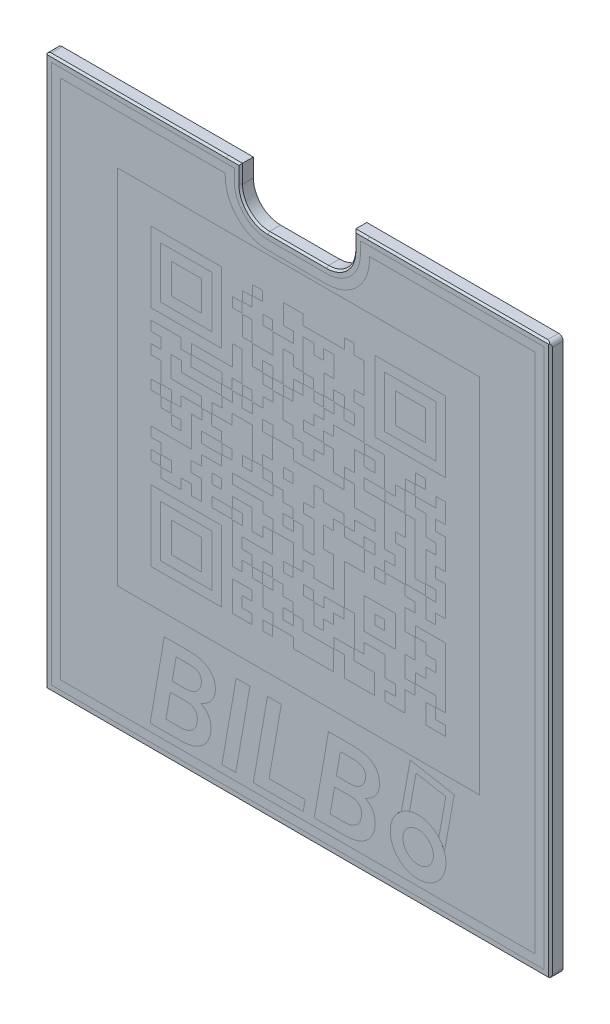
SolidWorks part; units mm, degrees
ref_plane "Front Plane" through (0, 0, 0) normal (0, 0, 1) x (1, 0, 0)
ref_plane "Top Plane" through (0, 0, 0) normal (0, 1, 0) x (1, 0, 0)
ref_plane "Right Plane" through (0, 0, 0) normal (1, 0, 0) x (0, 0, -1)
sketch "Sketch1" plane through (0, 0, 0) normal (0, 0, 1) x (1, 0, 0)
  line L0 (48, -68) -> (-48, -68) construction
  line L1 (56, -32.5) -> (56, -60) construction
  line L2 (56, 46) -> (56, -24.5) construction
  line L3 (-56, -24.5) -> (-56, 46) construction
  line L5 (-15, 54.4) -> (-15, 29) construction
  line L6 (-15, 29) -> (15, 29) construction
  line L7 (15, 29) -> (15, 54) construction
  line L8 (48, 54) -> (15, 54) construction
  line L9 (48, -68) -> (-48, -68) construction
  line L10 (56, -32.5) -> (56, -60) construction
  line L11 (56, 46) -> (56, -24.5) construction
  line L12 (-56, -24.5) -> (-56, 46) construction
  line L13 (-15, 54.4) -> (-48, 54.4) construction
  line L14 (-15, 54.4) -> (-15, 29) construction
  line L15 (-15, 29) -> (15, 29) construction
  line L16 (15, 29) -> (15, 54) construction
  line L17 (48, 54) -> (15, 54) construction
  line L18 (-15.25, 54.05) -> (-15.25, 28.75)
  line L19 (-55.65, 54.05) -> (-15.25, 54.05)
  line L20 (-55.65, 54.05) -> (-55.65, -67.65)
  line L21 (-55.65, -67.65) -> (55.825, -67.65)
  line L22 (55.825, 54.05) -> (55.825, -67.65)
  line L23 (-15.25, 28.75) -> (15.125, 28.75)
  line L24 (15.125, 28.75) -> (15.125, 54.05)
  line L25 (15.125, 54.05) -> (55.825, 54.05)
  arc A1 (-49.5246, -64.05) -> (-52.475, -61.2455) centre (-52, -63.7) ccw construction
  arc A2 (-53.35, 50.3) -> (-52, 48.95) centre (-52, 50.3) ccw construction
  circle A5 centre (-52, -63.7) radius 2.1 construction
  circle A6 centre (-52, 2.9) radius 2.15 construction
  circle A7 centre (52, 2.9) radius 2.15 construction
  circle A8 centre (52, 50.3) radius 2.1 construction
  circle A9 centre (-52, 50.3) radius 2.1 construction
  circle A10 centre (-52, 50.3) radius 1.35
  circle A11 centre (-52, 2.9) radius 1.35
  circle A12 centre (-52, -63.7) radius 1.35
  circle A13 centre (52, 50.3) radius 1.35
  circle A14 centre (52, 2.9) radius 1.35
  circle A15 centre (52, -63.7) radius 1.35
  circle A16 centre (-52, 2.9) radius 2.15 construction
  circle A17 centre (52, 2.9) radius 2.15 construction
  arc A18 (52, 48.95) -> (53.35, 50.3) centre (52, 50.3) ccw construction
  arc A19 (53.35, -65.8042) -> (53.35, -61.5958) centre (52, -63.7) ccw construction
  dimension "D5" = 2.7
  dimension "D1" = 0.35
  dimension "D2" = 0.35
  dimension "D3" = 0.35
  dimension "D4" = 0.35
  dimension "D6" = 0.25
  dimension "D7" = 0.25
  dimension "D8" = 0.25
extrude "Boss-Extrude1" add sketch "Sketch1" along normal blind 2.8
sketch "Sketch2" plane through (0, 0, 2.8) normal (0, 0, 1) x (1, 0, 0)
  line L5 (15.125, 28.75) -> (-15.25, 28.75) construction
  line L8 (-45.5, -63.25) -> (45.5, -63.25)
  line L9 (-45.5, -63.25) -> (-45.5, 27.75)
  line L10 (-45.5, 27.75) -> (45.5, 27.75)
  line L11 (45.5, -63.25) -> (45.5, 27.75)
  line L31 (-42, 24.25) -> (-28, 24.25)
  line L32 (-42, 24.25) -> (-42, 10.25)
  line L33 (-42, 10.25) -> (-28, 10.25)
  line L34 (-28, 24.25) -> (-28, 10.25)
  line L35 (-28, 24.25) -> (-14, 24.25)
  line L36 (-28, 24.25) -> (-28, 10.25)
  line L37 (-28, 10.25) -> (-14, 10.25)
  line L38 (-14, 24.25) -> (-14, 10.25)
  line L39 (-14, 24.25) -> (0, 24.25)
  line L40 (-14, 24.25) -> (-14, 10.25)
  line L41 (-14, 10.25) -> (0, 10.25)
  line L42 (0, 24.25) -> (0, 10.25)
  line L43 (0, 24.25) -> (14, 24.25)
  line L44 (0, 24.25) -> (0, 10.25)
  line L45 (0, 10.25) -> (14, 10.25)
  line L46 (14, 24.25) -> (14, 10.25)
  line L47 (14, 24.25) -> (28, 24.25)
  line L48 (14, 24.25) -> (14, 10.25)
  line L49 (14, 10.25) -> (28, 10.25)
  line L50 (28, 24.25) -> (28, 10.25)
  line L51 (28, 24.25) -> (42, 24.25)
  line L52 (28, 24.25) -> (28, 10.25)
  line L53 (28, 10.25) -> (42, 10.25)
  line L54 (42, 24.25) -> (42, 10.25)
  line L55 (-42, 10.25) -> (-28, 10.25)
  line L56 (-42, 10.25) -> (-42, -3.75)
  line L57 (-42, -3.75) -> (-28, -3.75)
  line L58 (-28, 10.25) -> (-28, -3.75)
  line L59 (-28, -3.75) -> (-14, -3.75)
  line L60 (-28, -3.75) -> (-28, 10.25)
  line L61 (-28, 10.25) -> (-14, 10.25)
  line L62 (-14, -3.75) -> (-14, 10.25)
  line L63 (-14, -3.75) -> (0, -3.75)
  line L64 (-14, -3.75) -> (-14, 10.25)
  line L65 (-14, 10.25) -> (0, 10.25)
  line L66 (0, -3.75) -> (0, 10.25)
  line L67 (0, -3.75) -> (14, -3.75)
  line L68 (0, -3.75) -> (0, 10.25)
  line L69 (0, 10.25) -> (14, 10.25)
  line L70 (14, -3.75) -> (14, 10.25)
  line L71 (14, -3.75) -> (28, -3.75)
  line L72 (14, -3.75) -> (14, 10.25)
  line L73 (14, 10.25) -> (28, 10.25)
  line L74 (28, -3.75) -> (28, 10.25)
  line L75 (28, -3.75) -> (42, -3.75)
  line L76 (28, -3.75) -> (28, 10.25)
  line L77 (28, 10.25) -> (42, 10.25)
  line L78 (42, -3.75) -> (42, 10.25)
  line L79 (42, -3.75) -> (28, -3.75)
  line L80 (42, -3.75) -> (42, -17.75)
  line L81 (42, -17.75) -> (28, -17.75)
  line L82 (28, -3.75) -> (28, -17.75)
  line L83 (14, -3.75) -> (28, -3.75)
  line L84 (14, -3.75) -> (14, -17.75)
  line L85 (14, -17.75) -> (28, -17.75)
  line L86 (28, -3.75) -> (28, -17.75)
  line L87 (0, -3.75) -> (14, -3.75)
  line L88 (0, -3.75) -> (0, -17.75)
  line L89 (0, -17.75) -> (14, -17.75)
  line L90 (14, -3.75) -> (14, -17.75)
  line L91 (-14, -3.75) -> (0, -3.75)
  line L92 (-14, -3.75) -> (-14, -17.75)
  line L93 (-14, -17.75) -> (0, -17.75)
  line L94 (0, -3.75) -> (0, -17.75)
  line L95 (-28, -3.75) -> (-14, -3.75)
  line L96 (-28, -3.75) -> (-28, -17.75)
  line L97 (-28, -17.75) -> (-14, -17.75)
  line L98 (-14, -3.75) -> (-14, -17.75)
  line L99 (-42, -3.75) -> (-28, -3.75)
  line L100 (-42, -3.75) -> (-42, -17.75)
  line L101 (-42, -17.75) -> (-28, -17.75)
  line L102 (-28, -3.75) -> (-28, -17.75)
  line L103 (-42, -17.75) -> (-28, -17.75)
  line L104 (-42, -17.75) -> (-42, -31.75)
  line L105 (-42, -31.75) -> (-28, -31.75)
  line L106 (-28, -17.75) -> (-28, -31.75)
  line L107 (-28, -31.75) -> (-14, -31.75)
  line L108 (-28, -31.75) -> (-28, -17.75)
  line L109 (-28, -17.75) -> (-14, -17.75)
  line L110 (-14, -31.75) -> (-14, -17.75)
  line L111 (-14, -17.75) -> (0, -17.75)
  line L112 (-14, -17.75) -> (-14, -31.75)
  line L113 (-14, -31.75) -> (0, -31.75)
  line L114 (0, -17.75) -> (0, -31.75)
  line L115 (0, -31.75) -> (14, -31.75)
  line L116 (0, -31.75) -> (0, -17.75)
  line L117 (0, -17.75) -> (14, -17.75)
  line L118 (14, -31.75) -> (14, -17.75)
  line L119 (14, -31.75) -> (28, -31.75)
  line L120 (14, -31.75) -> (14, -17.75)
  line L121 (14, -17.75) -> (28, -17.75)
  line L122 (28, -31.75) -> (28, -17.75)
  line L123 (28, -31.75) -> (42, -31.75)
  line L124 (28, -31.75) -> (28, -17.75)
  line L125 (28, -17.75) -> (42, -17.75)
  line L126 (42, -31.75) -> (42, -17.75)
  line L127 (-42, -31.75) -> (-28, -31.75)
  line L128 (-42, -31.75) -> (-42, -45.75)
  line L129 (-42, -45.75) -> (-28, -45.75)
  line L130 (-28, -31.75) -> (-28, -45.75)
  line L131 (-28, -45.75) -> (-14, -45.75)
  line L132 (-28, -45.75) -> (-28, -31.75)
  line L133 (-28, -31.75) -> (-14, -31.75)
  line L134 (-14, -45.75) -> (-14, -31.75)
  line L135 (-14, -45.75) -> (0, -45.75)
  line L136 (-14, -45.75) -> (-14, -31.75)
  line L137 (-14, -31.75) -> (0, -31.75)
  line L138 (0, -45.75) -> (0, -31.75)
  line L139 (0, -45.75) -> (14, -45.75)
  line L140 (0, -45.75) -> (0, -31.75)
  line L141 (0, -31.75) -> (14, -31.75)
  line L142 (14, -45.75) -> (14, -31.75)
  line L143 (14, -45.75) -> (28, -45.75)
  line L144 (14, -45.75) -> (14, -31.75)
  line L145 (14, -31.75) -> (28, -31.75)
  line L146 (28, -45.75) -> (28, -31.75)
  line L147 (28, -45.75) -> (42, -45.75)
  line L148 (28, -45.75) -> (28, -31.75)
  line L149 (28, -31.75) -> (42, -31.75)
  line L150 (42, -45.75) -> (42, -31.75)
  line L151 (42, -45.75) -> (28, -45.75)
  line L152 (42, -45.75) -> (42, -59.75)
  line L153 (42, -59.75) -> (28, -59.75)
  line L154 (28, -45.75) -> (28, -59.75)
  line L155 (28, -59.75) -> (14, -59.75)
  line L156 (28, -59.75) -> (28, -45.75)
  line L157 (28, -45.75) -> (14, -45.75)
  line L158 (14, -59.75) -> (14, -45.75)
  line L159 (0, -45.75) -> (14, -45.75)
  line L160 (0, -45.75) -> (0, -59.75)
  line L161 (0, -59.75) -> (14, -59.75)
  line L162 (14, -45.75) -> (14, -59.75)
  line L163 (-14, -45.75) -> (0, -45.75)
  line L164 (-14, -45.75) -> (-14, -59.75)
  line L165 (-14, -59.75) -> (0, -59.75)
  line L166 (0, -45.75) -> (0, -59.75)
  line L167 (-28, -45.75) -> (-14, -45.75)
  line L168 (-28, -45.75) -> (-28, -59.75)
  line L169 (-28, -59.75) -> (-14, -59.75)
  line L170 (-14, -45.75) -> (-14, -59.75)
  line L171 (-42, -45.75) -> (-28, -45.75)
  line L172 (-42, -45.75) -> (-42, -59.75)
  line L173 (-42, -59.75) -> (-28, -59.75)
  line L174 (-28, -45.75) -> (-28, -59.75)
  point P3 (0, 27.75)
  point P58 (-45.5, -17.75)
  dimension "D1" = 1
  dimension "D2" = 91
  dimension "D3" = 14
sketch "Sketch3" plane through (0, 0, 2.8) normal (0, 0, 1) x (1, 0, 0)
  circle A0 centre (-52, 50.3) radius 2.5
  circle A1 centre (-52, 2.9) radius 2.5
  circle A2 centre (-52, -63.7) radius 2.5
  circle A3 centre (52, -63.7) radius 2.5
  circle A4 centre (52, 2.9) radius 2.5
  circle A5 centre (52, 50.3) radius 2.5
  dimension "D1" = 5
extrude "Cut-Extrude1" cut sketch "Sketch3" against normal blind 2.2
sketch "Sketch4" plane through (0, 0, 0) normal (0, 0, -1) x (-1, 0, 0)
  line L0 (-15.125, 28.75) -> (15.25, 28.75) construction
  line L1 (-45.65, -57.65) -> (45.65, -57.65)
  line L2 (-45.65, -57.65) -> (-45.65, 27.75)
  line L3 (-45.65, 27.75) -> (45.65, 27.75)
  line L4 (45.65, -57.65) -> (45.65, 27.75)
  line L5 (-45.65, -57.65) -> (45.65, 27.75) construction
  line L6 (-45.65, 27.75) -> (45.65, -57.65) construction
  line L7 (55.65, 54.05) -> (55.65, -67.65) construction
  line L8 (55.65, -67.65) -> (-55.825, -67.65) construction
  point P0 (0, -14.95)
  point P9 (0, 27.75)
  dimension "D1" = 1
  dimension "D2" = 10
  dimension "D3" = 10
extrude "Cut-Extrude2" cut sketch "Sketch4" against normal blind 1.5
sketch "Sketch5" plane through (0, 0, 0.6) normal (0, 0, 1) x (1, 0, 0)
  line L2 (-53.35, 48.1958) -> (-53.35, 52.4042)
  line L4 (-50.65, 48.1958) -> (-50.65, 52.4042)
  line L5 (-53.35, 48.1958) -> (-50.65, 52.4042) construction
  line L6 (-53.35, 52.4042) -> (-50.65, 48.1958) construction
  line L8 (-53.35, 0.7958) -> (-53.35, 5.0042)
  line L10 (-50.65, 0.7958) -> (-50.65, 5.0042)
  line L11 (-53.35, 0.7958) -> (-50.65, 5.0042) construction
  line L12 (-53.35, 5.0042) -> (-50.65, 0.7958) construction
  line L14 (-53.35, -65.8042) -> (-53.35, -61.5958)
  line L16 (-50.65, -65.8042) -> (-50.65, -61.5958)
  line L17 (-53.35, -65.8042) -> (-50.65, -61.5958) construction
  line L18 (-53.35, -61.5958) -> (-50.65, -65.8042) construction
  circle A0 centre (-52, 50.3) radius 2.5 construction
  circle A1 centre (-52, 50.3) radius 1.35 construction
  arc A2 (-50.65, 52.4042) -> (-53.35, 52.4042) centre (-52, 50.3) ccw
  arc A3 (-53.35, 48.1958) -> (-50.65, 48.1958) centre (-52, 50.3) ccw
  circle A4 centre (-52, 2.9) radius 2.5 construction
  circle A5 centre (-52, 2.9) radius 1.35 construction
  circle A6 centre (-52, 2.9) radius 2.5 construction
  arc A7 (-50.65, 5.0042) -> (-53.35, 5.0042) centre (-52, 2.9) ccw
  arc A8 (-53.35, 0.7958) -> (-50.65, 0.7958) centre (-52, 2.9) ccw
  circle A9 centre (-52, -63.7) radius 2.5 construction
  circle A10 centre (-52, -63.7) radius 1.35 construction
  circle A11 centre (-52, -63.7) radius 2.5 construction
  arc A12 (-50.65, -61.5958) -> (-53.35, -61.5958) centre (-52, -63.7) ccw
  arc A13 (-53.35, -65.8042) -> (-50.65, -65.8042) centre (-52, -63.7) ccw
  point P0 (-52, 50.3)
  point P10 (-52, 2.9)
  point P22 (-52, -63.7)
extrude "Cut-Extrude3" cut sketch "Sketch5" against normal blind 0.2
sketch "Sketch6" plane through (0, 0, 0.4) normal (0, 0, 1) x (1, 0, 0)
  line L0 (-50.65, -65.8042) -> (-50.65, -61.5958) construction
  line L1 (-53.35, -65.05) -> (-50.65, -65.05)
  line L2 (-53.35, -65.05) -> (-53.35, -62.35)
  line L3 (-53.35, -62.35) -> (-50.65, -62.35)
  line L4 (-50.65, -65.05) -> (-50.65, -62.35)
  line L5 (-53.35, -65.05) -> (-50.65, -62.35) construction
  line L6 (-53.35, -62.35) -> (-50.65, -65.05) construction
  line L7 (-50.65, 0.7958) -> (-50.65, 5.0042) construction
  line L8 (-53.35, 1.55) -> (-50.65, 1.55)
  line L9 (-53.35, 1.55) -> (-53.35, 4.25)
  line L10 (-53.35, 4.25) -> (-50.65, 4.25)
  line L11 (-50.65, 1.55) -> (-50.65, 4.25)
  line L12 (-53.35, 1.55) -> (-50.65, 4.25) construction
  line L13 (-53.35, 4.25) -> (-50.65, 1.55) construction
  line L14 (-50.65, 48.1958) -> (-50.65, 52.4042) construction
  line L15 (-53.35, 48.95) -> (-50.65, 48.95)
  line L16 (-53.35, 48.95) -> (-53.35, 51.65)
  line L17 (-53.35, 51.65) -> (-50.65, 51.65)
  line L18 (-50.65, 48.95) -> (-50.65, 51.65)
  line L19 (-53.35, 48.95) -> (-50.65, 51.65) construction
  line L20 (-53.35, 51.65) -> (-50.65, 48.95) construction
  arc A0 (-50.65, -63.7) -> (-53.35, -63.7) centre (-52, -63.7) ccw construction
  arc A1 (-50.65, 2.9) -> (-53.35, 2.9) centre (-52, 2.9) ccw construction
  arc A2 (-50.65, 50.3) -> (-53.35, 50.3) centre (-52, 50.3) ccw construction
  point P0 (-52, -63.7)
  point P11 (-52, 2.9)
  point P22 (-52, 50.3)
extrude "Cut-Extrude4" cut sketch "Sketch6" against normal blind 0.2
mirror "Mirror1" about plane through (0, 0, 0) normal (1, 0, 0) of "Cut-Extrude4", "Cut-Extrude3"
chamfer "Chamfer1" distance 0.4 angle 45 8 edges at (0.0875, -67.65, 2.8) (55.825, -6.8, 2.8) (35.475, 54.05, 2.8) (15.125, 41.4, 2.8) (-0.0625, 28.75, 2.8) (-15.25, 41.4, 2.8) (-35.45, 54.05, 2.8) (-55.65, -6.8, 2.8)
sketch "Sketch11" plane through (0, 0, 2.8) normal (0, 0, 1) x (1, 0, 0)
  line L0 (15.125, 54.05) -> (55.825, 54.05) construction
  line L1 (-15.65, 28.35) -> (15.525, 28.35)
  line L2 (-15.65, 28.35) -> (-15.65, 54.05)
  line L3 (-15.65, 54.05) -> (15.525, 54.05)
  line L4 (15.525, 28.35) -> (15.525, 54.05)
  line L5 (15.525, 53.65) -> (15.525, 28.35) construction
extrude "Boss-Extrude4" add sketch "Sketch11" against normal up to surface (2.8 mm away) up to face at (0, -14.95, 0)
chamfer "Chamfer2" distance 0.4 angle 45 1 edges at (-0.0625, 54.05, 2.8)
sketch "Sketch12" plane through (0, 0, 2.8) normal (0, 0, 1) x (1, 0, 0)
  circle A0 centre (52, -63.7) radius 2.5 construction
  circle A1 centre (52, 50.3) radius 2.5 construction
  circle A2 centre (52, 2.9) radius 2.5 construction
  circle A3 centre (-52, -63.7) radius 2.5 construction
  circle A4 centre (-52, 2.9) radius 2.5 construction
  circle A5 centre (-52, 50.3) radius 2.5 construction
  circle A6 centre (52, -63.7) radius 2.5
  circle A7 centre (52, 50.3) radius 2.5
  circle A8 centre (52, 2.9) radius 2.5
  circle A9 centre (-52, -63.7) radius 2.5
  circle A10 centre (-52, 2.9) radius 2.5
  circle A11 centre (-52, 50.3) radius 2.5
extrude "Boss-Extrude5" add sketch "Sketch12" against normal up to surface (2.8 mm away) up to face at (0.0875, -6.8, 0)
sketch "Sketch13" plane through (0, 0, 0) normal (0, 0, -1) x (-1, 0, 0)
  line L0 (-55.825, -67.65) -> (-55.825, 54.05) construction
  line L1 (-50.825, 49.05) -> (50.825, 49.05) construction
  line L2 (-50.825, 49.05) -> (-50.825, -62.65) construction
  line L3 (-50.825, -62.65) -> (50.825, -62.65) construction
  line L4 (50.825, 49.05) -> (50.825, -62.65) construction
  line L5 (-55.825, 54.05) -> (55.65, 54.05) construction
  line L6 (55.65, -67.65) -> (-55.825, -67.65) construction
  circle A0 centre (-50.825, 49.05) radius 3.2
  circle A1 centre (50.825, 49.05) radius 3.2
  circle A2 centre (50.825, -62.65) radius 3.2
  circle A3 centre (-50.825, -62.65) radius 3.2
  circle A4 centre (-50.825, -6.8) radius 3.2
  circle A5 centre (50.825, -6.8) radius 3.2
  point P4 (0, 49.05)
  dimension "D1" = 6.4
  dimension "D2" = 5
  dimension "D3" = 5
  dimension "D4" = 5
extrude "Cut-Extrude7" cut sketch "Sketch13" against normal blind 1.2
sketch "Sketch14" plane through (0, 0, 2.8) normal (0, 0, 1) x (1, 0, 0)
  line L0 (-55.65, 54.05) -> (-15.65, 54.05) construction
  line L1 (-12.5, 54.05) -> (12.5, 54.05)
  line L2 (-12.5, 54.05) -> (-12.5, 44.05)
  line L3 (-12.5, 44.05) -> (12.5, 44.05)
  line L4 (12.5, 54.05) -> (12.5, 44.05)
  point P6 (0, 44.05)
  dimension "D1" = 25
  dimension "D2" = 10
extrude "Cut-Extrude8" cut sketch "Sketch14" against normal through all
fillet "Fillet1" radius 6 2 edges at (12.5, 44.05, 1.4) (-12.5, 44.05, 1.4)
chamfer "Chamfer3" distance 0.4 angle 45 5 edges at (-12.5, 51.85, 2.8) (12.5, 51.85, 2.8) (-10.7426, 45.8074, 2.8) (10.7426, 45.8074, 2.8) (0, 44.05, 2.8)
sketch "Sketch22" plane through (0, 0, 2.8) normal (0, 0, 1) x (1, 0, 0)
  line L0 (-39.7032, 39.7992) -> (40.1257, 39.7992)
  line L1 (40.1257, 39.7992) -> (40.1257, -40.0298)
  line L2 (40.1257, -40.0298) -> (-39.7032, -40.0298)
  line L3 (-39.7032, -40.0298) -> (-39.7032, 39.7992)
  line L4 (-32.2887, 30.1954) -> (-32.2887, 16.7799)
  line L5 (-32.2887, 16.7799) -> (-16.6839, 16.7799)
  line L6 (-16.6839, 16.7799) -> (-16.6839, 32.3847)
  line L7 (-16.6839, 32.3847) -> (-32.2887, 32.3847)
  line L8 (-32.2887, 32.3847) -> (-32.2887, 30.1954)
  line L9 (-9.8364, 30.2513) -> (-7.703, 30.2513)
  line L10 (-7.703, 30.2513) -> (-7.703, 32.3847)
  line L11 (-7.703, 32.3847) -> (-9.8364, 32.3847)
  line L12 (-9.8364, 32.3847) -> (-9.8364, 30.2513)
  line L13 (-3.1007, 30.1954) -> (-3.1007, 28.006)
  line L14 (-3.1007, 28.006) -> (-0.8554, 28.006)
  line L15 (-0.8554, 28.006) -> (-0.8554, 25.649)
  line L16 (-0.8554, 25.649) -> (-5.3459, 25.649)
  line L17 (-5.3459, 25.649) -> (-5.3459, 21.1585)
  line L18 (-5.3459, 21.1585) -> (-9.8364, 21.1585)
  line L19 (-9.8364, 21.1585) -> (-9.8364, 16.7799)
  line L20 (-9.8364, 16.7799) -> (-7.703, 16.7799)
  line L21 (-7.703, 16.7799) -> (-7.703, 19.0251)
  line L22 (-7.703, 19.0251) -> (-5.3459, 19.0251)
  line L23 (-5.3459, 19.0251) -> (-5.3459, 16.7799)
  line L24 (-5.3459, 16.7799) -> (-3.2125, 16.7799)
  line L25 (-3.2125, 16.7799) -> (-3.2125, 23.5156)
  line L26 (-3.2125, 23.5156) -> (-0.8554, 23.5156)
  line L27 (-0.8554, 23.5156) -> (-0.8554, 21.2703)
  line L28 (-0.8554, 21.2703) -> (1.278, 21.2703)
  line L29 (1.278, 21.2703) -> (1.278, 28.006)
  line L30 (1.278, 28.006) -> (3.635, 28.006)
  line L31 (3.635, 28.006) -> (3.635, 25.7608)
  line L32 (3.635, 25.7608) -> (5.7684, 25.7608)
  line L33 (5.7684, 25.7608) -> (5.7684, 28.006)
  line L34 (5.7684, 28.006) -> (8.1255, 28.006)
  line L35 (8.1255, 28.006) -> (8.1255, 23.4037)
  line L36 (8.1255, 23.4037) -> (5.8803, 23.4037)
  line L37 (5.8803, 23.4037) -> (5.8803, 19.0251)
  line L38 (5.8803, 19.0251) -> (8.0137, 19.0251)
  line L39 (8.0137, 19.0251) -> (8.0137, 21.2703)
  line L40 (8.0137, 21.2703) -> (10.3707, 21.2703)
  line L41 (10.3707, 21.2703) -> (10.3707, 19.0251)
  line L42 (10.3707, 19.0251) -> (12.616, 19.0251)
  line L43 (12.616, 19.0251) -> (12.616, 16.668)
  line L44 (12.616, 16.668) -> (10.2589, 16.668)
  line L45 (10.2589, 16.668) -> (10.2589, 18.9133)
  line L46 (10.2589, 18.9133) -> (8.1255, 18.9133)
  line L47 (8.1255, 18.9133) -> (8.1255, 16.668)
  line L48 (8.1255, 16.668) -> (5.8803, 16.668)
  line L49 (5.8803, 16.668) -> (5.8803, 14.4228)
  line L50 (5.8803, 14.4228) -> (3.635, 14.4228)
  line L51 (3.635, 14.4228) -> (3.635, 12.1776)
  line L52 (3.635, 12.1776) -> (1.3898, 12.1776)
  line L53 (1.3898, 12.1776) -> (1.3898, 10.0442)
  line L54 (1.3898, 10.0442) -> (5.7684, 10.0442)
  line L55 (5.7684, 10.0442) -> (5.7684, 12.2894)
  line L56 (5.7684, 12.2894) -> (8.0137, 12.2894)
  line L57 (8.0137, 12.2894) -> (8.0137, 14.5346)
  line L58 (8.0137, 14.5346) -> (14.7494, 14.5346)
  line L59 (14.7494, 14.5346) -> (14.7494, 21.1585)
  line L60 (14.7494, 21.1585) -> (12.5041, 21.1585)
  line L61 (12.5041, 21.1585) -> (12.5041, 23.5156)
  line L62 (12.5041, 23.5156) -> (14.7494, 23.5156)
  line L63 (14.7494, 23.5156) -> (14.7494, 30.1394)
  line L64 (14.7494, 30.1394) -> (12.5041, 30.1394)
  line L65 (12.5041, 30.1394) -> (12.5041, 32.3847)
  line L66 (12.5041, 32.3847) -> (10.3707, 32.3847)
  line L67 (10.3707, 32.3847) -> (10.3707, 30.1394)
  line L68 (10.3707, 30.1394) -> (1.278, 30.1394)
  line L69 (1.278, 30.1394) -> (1.278, 32.3847)
  line L70 (1.278, 32.3847) -> (-3.1007, 32.3847)
  line L71 (-3.1007, 32.3847) -> (-3.1007, 30.1954)
  line L72 (17.1064, 30.1954) -> (17.1064, 16.7799)
  line L73 (17.1064, 16.7799) -> (32.7113, 16.7799)
  line L74 (32.7113, 16.7799) -> (32.7113, 32.3847)
  line L75 (32.7113, 32.3847) -> (17.1064, 32.3847)
  line L76 (17.1064, 32.3847) -> (17.1064, 30.1954)
  line L77 (-30.0994, 30.2513) -> (-18.8173, 30.2513)
  line L78 (-18.8173, 30.2513) -> (-18.8173, 18.9133)
  line L79 (-18.8173, 18.9133) -> (-30.1553, 18.9133)
  line L80 (-30.1553, 18.9133) -> (-30.1553, 30.2513)
  line L81 (-30.1553, 30.2513) -> (-30.1273, 30.2513)
  line L82 (-30.1273, 30.2513) -> (-30.0994, 30.2513)
  line L83 (19.2958, 30.2513) -> (30.5778, 30.2513)
  line L84 (30.5778, 30.2513) -> (30.5778, 18.9133)
  line L85 (30.5778, 18.9133) -> (19.2398, 18.9133)
  line L86 (19.2398, 18.9133) -> (19.2398, 30.2513)
  line L87 (19.2398, 30.2513) -> (19.2679, 30.2513)
  line L88 (19.2679, 30.2513) -> (19.2958, 30.2513)
  line L89 (-12.0816, 28.006) -> (-9.9482, 28.006)
  line L90 (-9.9482, 28.006) -> (-9.9482, 30.1394)
  line L91 (-9.9482, 30.1394) -> (-12.0816, 30.1394)
  line L92 (-12.0816, 30.1394) -> (-12.0816, 28.006)
  line L93 (-27.7983, 25.7049) -> (-27.7983, 21.2703)
  line L94 (-27.7983, 21.2703) -> (-21.1744, 21.2703)
  line L95 (-21.1744, 21.2703) -> (-21.1744, 27.8942)
  line L96 (-21.1744, 27.8942) -> (-27.7983, 27.8942)
  line L97 (-27.7983, 27.8942) -> (-27.7983, 25.7049)
  line L98 (-14.3269, 25.7608) -> (-12.1934, 25.7608)
  line L99 (-12.1934, 25.7608) -> (-12.1934, 27.8942)
  line L100 (-12.1934, 27.8942) -> (-14.3269, 27.8942)
  line L101 (-14.3269, 27.8942) -> (-14.3269, 25.7608)
  line L102 (-7.5912, 25.7608) -> (-5.4577, 25.7608)
  line L103 (-5.4577, 25.7608) -> (-5.4577, 27.8942)
  line L104 (-5.4577, 27.8942) -> (-7.5912, 27.8942)
  line L105 (-7.5912, 27.8942) -> (-7.5912, 25.7608)
  line L106 (21.5969, 25.7049) -> (21.5969, 21.2703)
  line L107 (21.5969, 21.2703) -> (28.2208, 21.2703)
  line L108 (28.2208, 21.2703) -> (28.2208, 27.8942)
  line L109 (28.2208, 27.8942) -> (21.5969, 27.8942)
  line L110 (21.5969, 27.8942) -> (21.5969, 25.7049)
  line L111 (-12.0816, 23.4597) -> (-12.0816, 21.2703)
  line L112 (-12.0816, 21.2703) -> (-9.9482, 21.2703)
  line L113 (-9.9482, 21.2703) -> (-9.9482, 25.649)
  line L114 (-9.9482, 25.649) -> (-12.0816, 25.649)
  line L115 (-12.0816, 25.649) -> (-12.0816, 23.4597)
  line L116 (1.3898, 19.0251) -> (3.5232, 19.0251)
  line L117 (3.5232, 19.0251) -> (3.5232, 21.1585)
  line L118 (3.5232, 21.1585) -> (1.3898, 21.1585)
  line L119 (1.3898, 21.1585) -> (1.3898, 19.0251)
  line L120 (-14.3269, 16.7239) -> (-14.3269, 14.4228)
  line L121 (-14.3269, 14.4228) -> (-23.3078, 14.4228)
  line L122 (-23.3078, 14.4228) -> (-23.3078, 12.2894)
  line L123 (-23.3078, 12.2894) -> (-16.5721, 12.2894)
  line L124 (-16.5721, 12.2894) -> (-16.5721, 10.0442)
  line L125 (-16.5721, 10.0442) -> (-14.4387, 10.0442)
  line L126 (-14.4387, 10.0442) -> (-14.4387, 12.2894)
  line L127 (-14.4387, 12.2894) -> (-12.1934, 12.2894)
  line L128 (-12.1934, 12.2894) -> (-12.1934, 18.9133)
  line L129 (-12.1934, 18.9133) -> (-14.3269, 18.9133)
  line L130 (-14.3269, 18.9133) -> (-14.3269, 16.7239)
  line L131 (-0.8554, 16.7799) -> (1.278, 16.7799)
  line L132 (1.278, 16.7799) -> (1.278, 18.9133)
  line L133 (1.278, 18.9133) -> (-0.8554, 18.9133)
  line L134 (-0.8554, 18.9133) -> (-0.8554, 16.7799)
  line L135 (3.635, 16.7799) -> (5.7684, 16.7799)
  line L136 (5.7684, 16.7799) -> (5.7684, 18.9133)
  line L137 (5.7684, 18.9133) -> (3.635, 18.9133)
  line L138 (3.635, 18.9133) -> (3.635, 16.7799)
  line L139 (-7.5912, 14.5346) -> (-5.4577, 14.5346)
  line L140 (-5.4577, 14.5346) -> (-5.4577, 16.668)
  line L141 (-5.4577, 16.668) -> (-7.5912, 16.668)
  line L142 (-7.5912, 16.668) -> (-7.5912, 14.5346)
  line L143 (-3.1007, 14.5346) -> (-0.9673, 14.5346)
  line L144 (-0.9673, 14.5346) -> (-0.9673, 16.668)
  line L145 (-0.9673, 16.668) -> (-3.1007, 16.668)
  line L146 (-3.1007, 16.668) -> (-3.1007, 14.5346)
  line L147 (-32.2887, 12.2894) -> (-30.0435, 12.2894)
  line L148 (-30.0435, 12.2894) -> (-30.0435, 9.9323)
  line L149 (-30.0435, 9.9323) -> (-32.2887, 9.9323)
  line L150 (-32.2887, 9.9323) -> (-32.2887, 7.7989)
  line L151 (-32.2887, 7.7989) -> (-30.0435, 7.7989)
  line L152 (-30.0435, 7.7989) -> (-30.0435, 3.3085)
  line L153 (-30.0435, 3.3085) -> (-27.7983, 3.3085)
  line L154 (-27.7983, 3.3085) -> (-27.7983, 1.0632)
  line L155 (-27.7983, 1.0632) -> (-25.6649, 1.0632)
  line L156 (-25.6649, 1.0632) -> (-25.6649, 3.3085)
  line L157 (-25.6649, 3.3085) -> (-21.1744, 3.3085)
  line L158 (-21.1744, 3.3085) -> (-21.1744, 5.4419)
  line L159 (-21.1744, 5.4419) -> (-27.9101, 5.4419)
  line L160 (-27.9101, 5.4419) -> (-27.9101, 10.0442)
  line L161 (-27.9101, 10.0442) -> (-25.553, 10.0442)
  line L162 (-25.553, 10.0442) -> (-25.553, 7.7989)
  line L163 (-25.553, 7.7989) -> (-16.6839, 7.7989)
  line L164 (-16.6839, 7.7989) -> (-16.6839, 9.9323)
  line L165 (-16.6839, 9.9323) -> (-23.4196, 9.9323)
  line L166 (-23.4196, 9.9323) -> (-23.4196, 12.1776)
  line L167 (-23.4196, 12.1776) -> (-25.6649, 12.1776)
  line L168 (-25.6649, 12.1776) -> (-25.6649, 14.4228)
  line L169 (-25.6649, 14.4228) -> (-32.2887, 14.4228)
  line L170 (-32.2887, 14.4228) -> (-32.2887, 12.2894)
  line L171 (-5.8228, 12.1776) -> (-7.5912, 12.1776)
  line L172 (-7.5912, 12.1776) -> (-7.5912, 9.9323)
  line L173 (-7.5912, 9.9323) -> (-9.8364, 9.9323)
  line L174 (-9.8364, 9.9323) -> (-9.8364, 7.6871)
  line L175 (-9.8364, 7.6871) -> (-12.1934, 7.6871)
  line L176 (-12.1934, 7.6871) -> (-12.1934, 9.9323)
  line L177 (-12.1934, 9.9323) -> (-14.3269, 9.9323)
  line L178 (-14.3269, 9.9323) -> (-14.3269, 7.6871)
  line L179 (-14.3269, 7.6871) -> (-16.5721, 7.6871)
  line L180 (-16.5721, 7.6871) -> (-16.5721, 5.4419)
  line L181 (-16.5721, 5.4419) -> (-18.8173, 5.4419)
  line L182 (-18.8173, 5.4419) -> (-18.8173, 3.3084)
  line L183 (-18.8173, 3.3084) -> (-14.4387, 3.3084)
  line L184 (-14.4387, 3.3084) -> (-14.4387, 5.5537)
  line L185 (-14.4387, 5.5537) -> (-9.8364, 5.5537)
  line L186 (-9.8364, 5.5537) -> (-9.8364, -1.182)
  line L187 (-9.8364, -1.182) -> (-7.703, -1.182)
  line L188 (-7.703, -1.182) -> (-7.703, 1.0632)
  line L189 (-7.703, 1.0632) -> (-5.4577, 1.0632)
  line L190 (-5.4577, 1.0632) -> (-5.4577, 5.4419)
  line L191 (-5.4577, 5.4419) -> (-7.703, 5.4419)
  line L192 (-7.703, 5.4419) -> (-7.703, 7.7989)
  line L193 (-7.703, 7.7989) -> (-5.3459, 7.7989)
  line L194 (-5.3459, 7.7989) -> (-5.3459, 5.5537)
  line L195 (-5.3459, 5.5537) -> (-0.8554, 5.5537)
  line L196 (-0.8554, 5.5537) -> (-0.8554, 3.3084)
  line L197 (-0.8554, 3.3084) -> (10.2589, 3.3084)
  line L198 (10.2589, 3.3084) -> (10.2589, 5.4419)
  line L199 (10.2589, 5.4419) -> (8.0137, 5.4419)
  line L200 (8.0137, 5.4419) -> (8.0137, 9.9323)
  line L201 (8.0137, 9.9323) -> (5.8803, 9.9323)
  line L202 (5.8803, 9.9323) -> (5.8803, 7.6871)
  line L203 (5.8803, 7.6871) -> (3.635, 7.6871)
  line L204 (3.635, 7.6871) -> (3.635, 5.4419)
  line L205 (3.635, 5.4419) -> (1.278, 5.4419)
  line L206 (1.278, 5.4419) -> (1.278, 7.6871)
  line L207 (1.278, 7.6871) -> (-0.9673, 7.6871)
  line L208 (-0.9673, 7.6871) -> (-0.9673, 9.9323)
  line L209 (-0.9673, 9.9323) -> (-3.2125, 9.9323)
  line L210 (-3.2125, 9.9323) -> (-3.2125, 14.4228)
  line L211 (-3.2125, 14.4228) -> (-5.3459, 14.4228)
  line L212 (-5.3459, 14.4228) -> (-5.3459, 12.2335)
  line L213 (14.8612, 12.2894) -> (17.1064, 12.2894)
  line L214 (17.1064, 12.2894) -> (17.1064, 9.9323)
  line L215 (17.1064, 9.9323) -> (14.7494, 9.9323)
  line L216 (14.7494, 9.9323) -> (14.7494, 12.1776)
  line L217 (14.7494, 12.1776) -> (12.616, 12.1776)
  line L218 (12.616, 12.1776) -> (12.616, 7.6871)
  line L219 (12.616, 7.6871) -> (10.3707, 7.6871)
  line L220 (10.3707, 7.6871) -> (10.3707, 5.5537)
  line L221 (10.3707, 5.5537) -> (12.616, 5.5537)
  line L222 (12.616, 5.5537) -> (12.616, 1.0632)
  line L223 (12.616, 1.0632) -> (17.1064, 1.0632)
  line L224 (17.1064, 1.0632) -> (17.1064, -1.2938)
  line L225 (17.1064, -1.2938) -> (12.616, -1.2938)
  line L226 (12.616, -1.2938) -> (12.616, -3.5391)
  line L227 (12.616, -3.5391) -> (10.3707, -3.5391)
  line L228 (10.3707, -3.5391) -> (10.3707, -5.6725)
  line L229 (10.3707, -5.6725) -> (14.7494, -5.6725)
  line L230 (14.7494, -5.6725) -> (14.7494, -3.4273)
  line L231 (14.7494, -3.4273) -> (17.1064, -3.4273)
  line L232 (17.1064, -3.4273) -> (17.1064, -5.7843)
  line L233 (17.1064, -5.7843) -> (14.8612, -5.7843)
  line L234 (14.8612, -5.7843) -> (14.8612, -10.2748)
  line L235 (14.8612, -10.2748) -> (10.3707, -10.2748)
  line L236 (10.3707, -10.2748) -> (10.3707, -19.1439)
  line L237 (10.3707, -19.1439) -> (12.616, -19.1439)
  line L238 (12.616, -19.1439) -> (12.616, -25.8796)
  line L239 (12.616, -25.8796) -> (14.7494, -25.8796)
  line L240 (14.7494, -25.8796) -> (14.7494, -23.6344)
  line L241 (14.7494, -23.6344) -> (19.3517, -23.6344)
  line L242 (19.3517, -23.6344) -> (19.3517, -28.1248)
  line L243 (19.3517, -28.1248) -> (21.5969, -28.1248)
  line L244 (21.5969, -28.1248) -> (21.5969, -30.4819)
  line L245 (21.5969, -30.4819) -> (19.3517, -30.4819)
  line L246 (19.3517, -30.4819) -> (19.3517, -32.6153)
  line L247 (19.3517, -32.6153) -> (23.7303, -32.6153)
  line L248 (23.7303, -32.6153) -> (23.7303, -28.1248)
  line L249 (23.7303, -28.1248) -> (25.9756, -28.1248)
  line L250 (25.9756, -28.1248) -> (25.9756, -25.9914)
  line L251 (25.9756, -25.9914) -> (23.7303, -25.9914)
  line L252 (23.7303, -25.9914) -> (23.7303, -21.3891)
  line L253 (23.7303, -21.3891) -> (25.9756, -21.3891)
  line L254 (25.9756, -21.3891) -> (25.9756, -17.0105)
  line L255 (25.9756, -17.0105) -> (23.7303, -17.0105)
  line L256 (23.7303, -17.0105) -> (23.7303, -12.4082)
  line L257 (23.7303, -12.4082) -> (25.9756, -12.4082)
  line L258 (25.9756, -12.4082) -> (25.9756, -10.2748)
  line L259 (25.9756, -10.2748) -> (23.7303, -10.2748)
  line L260 (23.7303, -10.2748) -> (23.7303, -8.0296)
  line L261 (23.7303, -8.0296) -> (19.3517, -8.0296)
  line L262 (19.3517, -8.0296) -> (19.3517, -10.2748)
  line L263 (19.3517, -10.2748) -> (16.9946, -10.2748)
  line L264 (16.9946, -10.2748) -> (16.9946, -7.9177)
  line L265 (16.9946, -7.9177) -> (19.2398, -7.9177)
  line L266 (19.2398, -7.9177) -> (19.2398, -5.6725)
  line L267 (19.2398, -5.6725) -> (21.4851, -5.6725)
  line L268 (21.4851, -5.6725) -> (21.4851, -3.5391)
  line L269 (21.4851, -3.5391) -> (19.2398, -3.5391)
  line L270 (19.2398, -3.5391) -> (19.2398, 5.4419)
  line L271 (19.2398, 5.4419) -> (14.7494, 5.4419)
  line L272 (14.7494, 5.4419) -> (14.7494, 7.7989)
  line L273 (14.7494, 7.7989) -> (19.2398, 7.7989)
  line L274 (19.2398, 7.7989) -> (19.2398, 14.4228)
  line L275 (19.2398, 14.4228) -> (14.8612, 14.4228)
  line L276 (14.8612, 14.4228) -> (14.8612, 12.2894)
  line L277 (26.0874, 12.2894) -> (28.2208, 12.2894)
  line L278 (28.2208, 12.2894) -> (28.2208, 14.4228)
  line L279 (28.2208, 14.4228) -> (26.0874, 14.4228)
  line L280 (26.0874, 14.4228) -> (26.0874, 12.2894)
  line L281 (-12.0816, 10.0442) -> (-9.9482, 10.0442)
  line L282 (-9.9482, 10.0442) -> (-9.9482, 12.1776)
  line L283 (-9.9482, 12.1776) -> (-12.0816, 12.1776)
  line L284 (-12.0816, 12.1776) -> (-12.0816, 10.0442)
  line L285 (23.8421, 10.0442) -> (25.9756, 10.0442)
  line L286 (25.9756, 10.0442) -> (25.9756, 12.1776)
  line L287 (25.9756, 12.1776) -> (23.8421, 12.1776)
  line L288 (23.8421, 12.1776) -> (23.8421, 10.0442)
  line L289 (30.101, 9.9323) -> (26.0874, 9.9323)
  line L290 (26.0874, 9.9323) -> (26.0874, 7.7989)
  line L291 (26.0874, 7.7989) -> (28.3326, 7.7989)
  line L292 (28.3326, 7.7989) -> (28.3326, 3.3085)
  line L293 (28.3326, 3.3085) -> (30.5778, 3.3085)
  line L294 (30.5778, 3.3085) -> (30.5778, 0.9514)
  line L295 (30.5778, 0.9514) -> (28.3326, 0.9514)
  line L296 (28.3326, 0.9514) -> (28.3326, -5.6725)
  line L297 (28.3326, -5.6725) -> (30.5778, -5.6725)
  line L298 (30.5778, -5.6725) -> (30.5778, -8.0295)
  line L299 (30.5778, -8.0295) -> (28.3326, -8.0295)
  line L300 (28.3326, -8.0295) -> (28.3326, -12.4082)
  line L301 (28.3326, -12.4082) -> (30.466, -12.4082)
  line L302 (30.466, -12.4082) -> (30.466, -10.163)
  line L303 (30.466, -10.163) -> (32.7113, -10.163)
  line L304 (32.7113, -10.163) -> (32.7113, -3.5391)
  line L305 (32.7113, -3.5391) -> (30.466, -3.5391)
  line L306 (30.466, -3.5391) -> (30.466, -1.182)
  line L307 (30.466, -1.182) -> (32.7113, -1.182)
  line L308 (32.7113, -1.182) -> (32.7113, 5.4419)
  line L309 (32.7113, 5.4419) -> (30.466, 5.4419)
  line L310 (30.466, 5.4419) -> (30.466, 7.7989)
  line L311 (30.466, 7.7989) -> (32.7113, 7.7989)
  line L312 (32.7113, 7.7989) -> (32.7113, 12.1776)
  line L313 (32.7113, 12.1776) -> (30.5778, 12.1776)
  line L314 (30.5778, 12.1776) -> (30.5778, 9.9882)
  line L315 (21.12, 7.6871) -> (19.3517, 7.6871)
  line L316 (19.3517, 7.6871) -> (19.3517, 5.5537)
  line L317 (19.3517, 5.5537) -> (23.7303, 5.5537)
  line L318 (23.7303, 5.5537) -> (23.7303, 9.9323)
  line L319 (23.7303, 9.9323) -> (21.5969, 9.9323)
  line L320 (21.5969, 9.9323) -> (21.5969, 7.743)
  line L321 (23.8421, 3.2525) -> (23.8421, 0.9514)
  line L322 (23.8421, 0.9514) -> (21.5969, 0.9514)
  line L323 (21.5969, 0.9514) -> (21.5969, -1.182)
  line L324 (21.5969, -1.182) -> (23.8421, -1.182)
  line L325 (23.8421, -1.182) -> (23.8421, -7.9177)
  line L326 (23.8421, -7.9177) -> (28.2208, -7.9177)
  line L327 (28.2208, -7.9177) -> (28.2208, -5.7843)
  line L328 (28.2208, -5.7843) -> (25.9756, -5.7843)
  line L329 (25.9756, -5.7843) -> (25.9756, 5.4419)
  line L330 (25.9756, 5.4419) -> (23.8421, 5.4419)
  line L331 (23.8421, 5.4419) -> (23.8421, 3.2525)
  line L332 (-32.2887, 1.0632) -> (-30.1553, 1.0632)
  line L333 (-30.1553, 1.0632) -> (-30.1553, 3.1966)
  line L334 (-30.1553, 3.1966) -> (-32.2887, 3.1966)
  line L335 (-32.2887, 3.1966) -> (-32.2887, 1.0632)
  line L336 (-21.5395, 0.9514) -> (-23.3078, 0.9514)
  line L337 (-23.3078, 0.9514) -> (-23.3078, -5.7843)
  line L338 (-23.3078, -5.7843) -> (-32.2887, -5.7843)
  line L339 (-32.2887, -5.7843) -> (-32.2887, -7.9177)
  line L340 (-32.2887, -7.9177) -> (-30.0435, -7.9177)
  line L341 (-30.0435, -7.9177) -> (-30.0435, -10.163)
  line L342 (-30.0435, -10.163) -> (-27.7983, -10.163)
  line L343 (-27.7983, -10.163) -> (-27.7983, -12.52)
  line L344 (-27.7983, -12.52) -> (-30.0435, -12.52)
  line L345 (-30.0435, -12.52) -> (-30.0435, -14.6534)
  line L346 (-30.0435, -14.6534) -> (-25.6649, -14.6534)
  line L347 (-25.6649, -14.6534) -> (-25.6649, -12.4082)
  line L348 (-25.6649, -12.4082) -> (-23.3078, -12.4082)
  line L349 (-23.3078, -12.4082) -> (-23.3078, -14.6534)
  line L350 (-23.3078, -14.6534) -> (-21.1744, -14.6534)
  line L351 (-21.1744, -14.6534) -> (-21.1744, -10.2748)
  line L352 (-21.1744, -10.2748) -> (-23.4196, -10.2748)
  line L353 (-23.4196, -10.2748) -> (-23.4196, -7.9177)
  line L354 (-23.4196, -7.9177) -> (-21.1744, -7.9177)
  line L355 (-21.1744, -7.9177) -> (-21.1744, -5.6725)
  line L356 (-21.1744, -5.6725) -> (-16.6839, -5.6725)
  line L357 (-16.6839, -5.6725) -> (-16.6839, -3.5391)
  line L358 (-16.6839, -3.5391) -> (-21.1744, -3.5391)
  line L359 (-21.1744, -3.5391) -> (-21.1744, -1.182)
  line L360 (-21.1744, -1.182) -> (-16.6839, -1.182)
  line L361 (-16.6839, -1.182) -> (-16.6839, 0.9514)
  line L362 (-16.6839, 0.9514) -> (-18.9292, 0.9514)
  line L363 (-18.9292, 0.9514) -> (-18.9292, 3.1966)
  line L364 (-18.9292, 3.1966) -> (-21.0626, 3.1966)
  line L365 (-21.0626, 3.1966) -> (-21.0626, 1.0073)
  line L366 (-30.0435, -1.182) -> (-27.9101, -1.182)
  line L367 (-27.9101, -1.182) -> (-27.9101, 0.9514)
  line L368 (-27.9101, 0.9514) -> (-30.0435, 0.9514)
  line L369 (-30.0435, 0.9514) -> (-30.0435, -1.182)
  line L370 (-3.1007, -1.182) -> (-0.9673, -1.182)
  line L371 (-0.9673, -1.182) -> (-0.9673, 0.9514)
  line L372 (-0.9673, 0.9514) -> (-3.1007, 0.9514)
  line L373 (-3.1007, 0.9514) -> (-3.1007, -1.182)
  line L374 (3.635, -1.2379) -> (3.635, -3.5391)
  line L375 (3.635, -3.5391) -> (1.3898, -3.5391)
  line L376 (1.3898, -3.5391) -> (1.3898, -5.6725)
  line L377 (1.3898, -5.6725) -> (3.635, -5.6725)
  line L378 (3.635, -5.6725) -> (3.635, -12.52)
  line L379 (3.635, -12.52) -> (1.278, -12.52)
  line L380 (1.278, -12.52) -> (1.278, -8.0295)
  line L381 (1.278, -8.0295) -> (-0.8554, -8.0295)
  line L382 (-0.8554, -8.0295) -> (-0.8554, -10.2748)
  line L383 (-0.8554, -10.2748) -> (-3.2125, -10.2748)
  line L384 (-3.2125, -10.2748) -> (-3.2125, -7.9177)
  line L385 (-3.2125, -7.9177) -> (-0.9673, -7.9177)
  line L386 (-0.9673, -7.9177) -> (-0.9673, -5.7843)
  line L387 (-0.9673, -5.7843) -> (-3.2125, -5.7843)
  line L388 (-3.2125, -5.7843) -> (-3.2125, -3.5391)
  line L389 (-3.2125, -3.5391) -> (-5.3459, -3.5391)
  line L390 (-5.3459, -3.5391) -> (-5.3459, -5.7843)
  line L391 (-5.3459, -5.7843) -> (-14.3269, -5.7843)
  line L392 (-14.3269, -5.7843) -> (-14.3269, -7.9177)
  line L393 (-14.3269, -7.9177) -> (-7.5912, -7.9177)
  line L394 (-7.5912, -7.9177) -> (-7.5912, -10.163)
  line L395 (-7.5912, -10.163) -> (-5.3459, -10.163)
  line L396 (-5.3459, -10.163) -> (-5.3459, -12.4082)
  line L397 (-5.3459, -12.4082) -> (-0.8554, -12.4082)
  line L398 (-0.8554, -12.4082) -> (-0.8554, -16.8987)
  line L399 (-0.8554, -16.8987) -> (1.278, -16.8987)
  line L400 (1.278, -16.8987) -> (1.278, -14.6534)
  line L401 (1.278, -14.6534) -> (3.635, -14.6534)
  line L402 (3.635, -14.6534) -> (3.635, -16.8987)
  line L403 (3.635, -16.8987) -> (8.0137, -16.8987)
  line L404 (8.0137, -16.8987) -> (8.0137, -10.2748)
  line L405 (8.0137, -10.2748) -> (5.7684, -10.2748)
  line L406 (5.7684, -10.2748) -> (5.7684, -5.6725)
  line L407 (5.7684, -5.6725) -> (8.0137, -5.6725)
  line L408 (8.0137, -5.6725) -> (8.0137, -3.4272)
  line L409 (8.0137, -3.4272) -> (10.2589, -3.4272)
  line L410 (10.2589, -3.4272) -> (10.2589, -1.2938)
  line L411 (10.2589, -1.2938) -> (5.7684, -1.2938)
  line L412 (5.7684, -1.2938) -> (5.7684, 0.9514)
  line L413 (5.7684, 0.9514) -> (3.635, 0.9514)
  line L414 (3.635, 0.9514) -> (3.635, -1.2379)
  line L415 (-27.7983, -3.4273) -> (-25.6649, -3.4273)
  line L416 (-25.6649, -3.4273) -> (-25.6649, -1.2938)
  line L417 (-25.6649, -1.2938) -> (-27.7983, -1.2938)
  line L418 (-27.7983, -1.2938) -> (-27.7983, -3.4273)
  line L419 (-16.5721, -3.4273) -> (-14.4387, -3.4273)
  line L420 (-14.4387, -3.4273) -> (-14.4387, -1.2938)
  line L421 (-14.4387, -1.2938) -> (-16.5721, -1.2938)
  line L422 (-16.5721, -1.2938) -> (-16.5721, -3.4273)
  line L423 (-12.0816, -3.4273) -> (-9.9482, -3.4273)
  line L424 (-9.9482, -3.4273) -> (-9.9482, -1.2938)
  line L425 (-9.9482, -1.2938) -> (-12.0816, -1.2938)
  line L426 (-12.0816, -1.2938) -> (-12.0816, -3.4273)
  line L427 (-7.5912, -3.4273) -> (-5.4577, -3.4273)
  line L428 (-5.4577, -3.4273) -> (-5.4577, -1.2938)
  line L429 (-5.4577, -1.2938) -> (-7.5912, -1.2938)
  line L430 (-7.5912, -1.2938) -> (-7.5912, -3.4273)
  line L431 (-18.8173, -10.163) -> (-16.6839, -10.163)
  line L432 (-16.6839, -10.163) -> (-16.6839, -8.0296)
  line L433 (-16.6839, -8.0296) -> (-18.8173, -8.0296)
  line L434 (-18.8173, -8.0296) -> (-18.8173, -10.163)
  line L435 (-32.2887, -12.4082) -> (-30.1553, -12.4082)
  line L436 (-30.1553, -12.4082) -> (-30.1553, -10.2748)
  line L437 (-30.1553, -10.2748) -> (-32.2887, -10.2748)
  line L438 (-32.2887, -10.2748) -> (-32.2887, -12.4082)
  line L439 (-14.3269, -12.4082) -> (-12.0816, -12.4082)
  line L440 (-12.0816, -12.4082) -> (-12.0816, -14.7653)
  line L441 (-12.0816, -14.7653) -> (-14.3269, -14.7653)
  line L442 (-14.3269, -14.7653) -> (-14.3269, -23.6344)
  line L443 (-14.3269, -23.6344) -> (-12.1934, -23.6344)
  line L444 (-12.1934, -23.6344) -> (-12.1934, -21.3891)
  line L445 (-12.1934, -21.3891) -> (-9.9482, -21.3891)
  line L446 (-9.9482, -21.3891) -> (-9.9482, -19.2557)
  line L447 (-9.9482, -19.2557) -> (-12.1934, -19.2557)
  line L448 (-12.1934, -19.2557) -> (-12.1934, -16.8987)
  line L449 (-12.1934, -16.8987) -> (-5.4577, -16.8987)
  line L450 (-5.4577, -16.8987) -> (-5.4577, -12.52)
  line L451 (-5.4577, -12.52) -> (-7.5912, -12.52)
  line L452 (-7.5912, -12.52) -> (-7.5912, -14.7653)
  line L453 (-7.5912, -14.7653) -> (-9.9482, -14.7653)
  line L454 (-9.9482, -14.7653) -> (-9.9482, -10.2748)
  line L455 (-9.9482, -10.2748) -> (-14.3269, -10.2748)
  line L456 (-14.3269, -10.2748) -> (-14.3269, -12.4082)
  line L457 (-18.8173, -14.6534) -> (-14.4387, -14.6534)
  line L458 (-14.4387, -14.6534) -> (-14.4387, -12.52)
  line L459 (-14.4387, -12.52) -> (-18.8173, -12.52)
  line L460 (14.8053, -14.6534) -> (21.5969, -14.6534)
  line L461 (21.5969, -14.6534) -> (21.5969, -21.501)
  line L462 (21.5969, -21.501) -> (14.7494, -21.501)
  line L463 (14.7494, -21.501) -> (14.7494, -14.6534)
  line L464 (14.7494, -14.6534) -> (14.7774, -14.6534)
  line L465 (14.7774, -14.6534) -> (14.8053, -14.6534)
  line L466 (26.0874, -16.8987) -> (28.3326, -16.8987)
  line L467 (28.3326, -16.8987) -> (28.3326, -19.1439)
  line L468 (28.3326, -19.1439) -> (30.5778, -19.1439)
  line L469 (30.5778, -19.1439) -> (30.5778, -21.501)
  line L470 (30.5778, -21.501) -> (28.3326, -21.501)
  line L471 (28.3326, -21.501) -> (28.3326, -23.7462)
  line L472 (28.3326, -23.7462) -> (26.0874, -23.7462)
  line L473 (26.0874, -23.7462) -> (26.0874, -25.8796)
  line L474 (26.0874, -25.8796) -> (30.5778, -25.8796)
  line L475 (30.5778, -25.8796) -> (30.5778, -28.1248)
  line L476 (30.5778, -28.1248) -> (32.7113, -28.1248)
  line L477 (32.7113, -28.1248) -> (32.7113, -14.7653)
  line L478 (32.7113, -14.7653) -> (26.0874, -14.7653)
  line L479 (26.0874, -14.7653) -> (26.0874, -16.8987)
  line L480 (-32.2887, -19.1998) -> (-32.2887, -32.6153)
  line L481 (-32.2887, -32.6153) -> (-16.6839, -32.6153)
  line L482 (-16.6839, -32.6153) -> (-16.6839, -17.0105)
  line L483 (-16.6839, -17.0105) -> (-32.2887, -17.0105)
  line L484 (-32.2887, -17.0105) -> (-32.2887, -19.1998)
  line L485 (-3.1007, -19.1439) -> (-0.9673, -19.1439)
  line L486 (-0.9673, -19.1439) -> (-0.9673, -17.0105)
  line L487 (-0.9673, -17.0105) -> (-3.1007, -17.0105)
  line L488 (-3.1007, -17.0105) -> (-3.1007, -19.1439)
  line L489 (17.1064, -19.1439) -> (19.2398, -19.1439)
  line L490 (19.2398, -19.1439) -> (19.2398, -17.0105)
  line L491 (19.2398, -17.0105) -> (17.1064, -17.0105)
  line L492 (17.1064, -17.0105) -> (17.1064, -19.1439)
  line L493 (-30.0994, -19.1439) -> (-18.8173, -19.1439)
  line L494 (-18.8173, -19.1439) -> (-18.8173, -30.4819)
  line L495 (-18.8173, -30.4819) -> (-30.1553, -30.4819)
  line L496 (-30.1553, -30.4819) -> (-30.1553, -19.1439)
  line L497 (-30.1553, -19.1439) -> (-30.1273, -19.1439)
  line L498 (-30.1273, -19.1439) -> (-30.0994, -19.1439)
  line L499 (-7.5912, -21.3891) -> (-5.4577, -21.3891)
  line L500 (-5.4577, -21.3891) -> (-5.4577, -19.2557)
  line L501 (-5.4577, -19.2557) -> (-7.5912, -19.2557)
  line L502 (-7.5912, -19.2557) -> (-7.5912, -21.3891)
  line L503 (1.3898, -21.3891) -> (3.5232, -21.3891)
  line L504 (3.5232, -21.3891) -> (3.5232, -19.2557)
  line L505 (3.5232, -19.2557) -> (1.3898, -19.2557)
  line L506 (1.3898, -19.2557) -> (1.3898, -21.3891)
  line L507 (5.4034, -21.501) -> (3.635, -21.501)
  line L508 (3.635, -21.501) -> (3.635, -25.8796)
  line L509 (3.635, -25.8796) -> (5.7684, -25.8796)
  line L510 (5.7684, -25.8796) -> (5.7684, -23.6344)
  line L511 (5.7684, -23.6344) -> (8.0137, -23.6344)
  line L512 (8.0137, -23.6344) -> (8.0137, -21.3891)
  line L513 (8.0137, -21.3891) -> (10.2589, -21.3891)
  line L514 (10.2589, -21.3891) -> (10.2589, -19.2557)
  line L515 (10.2589, -19.2557) -> (5.8803, -19.2557)
  line L516 (5.8803, -19.2557) -> (5.8803, -21.4451)
  line L517 (-27.7983, -23.6903) -> (-27.7983, -28.1248)
  line L518 (-27.7983, -28.1248) -> (-21.1744, -28.1248)
  line L519 (-21.1744, -28.1248) -> (-21.1744, -21.501)
  line L520 (-21.1744, -21.501) -> (-27.7983, -21.501)
  line L521 (-27.7983, -21.501) -> (-27.7983, -23.6903)
  line L522 (-9.8364, -23.6344) -> (-7.703, -23.6344)
  line L523 (-7.703, -23.6344) -> (-7.703, -21.501)
  line L524 (-7.703, -21.501) -> (-9.8364, -21.501)
  line L525 (-9.8364, -21.501) -> (-9.8364, -23.6344)
  line L526 (-5.8228, -23.7462) -> (-7.5912, -23.7462)
  line L527 (-7.5912, -23.7462) -> (-7.5912, -28.1248)
  line L528 (-7.5912, -28.1248) -> (-5.3459, -28.1248)
  line L529 (-5.3459, -28.1248) -> (-5.3459, -30.3701)
  line L530 (-5.3459, -30.3701) -> (-0.8554, -30.3701)
  line L531 (-0.8554, -30.3701) -> (-0.8554, -32.6153)
  line L532 (-0.8554, -32.6153) -> (8.0137, -32.6153)
  line L533 (8.0137, -32.6153) -> (8.0137, -28.2367)
  line L534 (8.0137, -28.2367) -> (1.278, -28.2367)
  line L535 (1.278, -28.2367) -> (1.278, -25.9914)
  line L536 (1.278, -25.9914) -> (-0.8554, -25.9914)
  line L537 (-0.8554, -25.9914) -> (-0.8554, -28.2367)
  line L538 (-0.8554, -28.2367) -> (-3.2125, -28.2367)
  line L539 (-3.2125, -28.2367) -> (-3.2125, -25.8796)
  line L540 (-3.2125, -25.8796) -> (-0.9673, -25.8796)
  line L541 (-0.9673, -25.8796) -> (-0.9673, -23.7462)
  line L542 (-0.9673, -23.7462) -> (-3.2125, -23.7462)
  line L543 (-3.2125, -23.7462) -> (-3.2125, -21.501)
  line L544 (-3.2125, -21.501) -> (-5.3459, -21.501)
  line L545 (-5.3459, -21.501) -> (-5.3459, -23.6903)
  line L546 (-14.3269, -28.1808) -> (-14.3269, -32.6153)
  line L547 (-14.3269, -32.6153) -> (-9.9482, -32.6153)
  line L548 (-9.9482, -32.6153) -> (-9.9482, -30.4819)
  line L549 (-9.9482, -30.4819) -> (-12.1934, -30.4819)
  line L550 (-12.1934, -30.4819) -> (-12.1934, -28.1248)
  line L551 (-12.1934, -28.1248) -> (-9.9482, -28.1248)
  line L552 (-9.9482, -28.1248) -> (-9.9482, -25.9914)
  line L553 (-9.9482, -25.9914) -> (-14.3269, -25.9914)
  line L554 (-14.3269, -25.9914) -> (-14.3269, -28.1808)
  line L555 (8.1255, -28.1248) -> (10.3707, -28.1248)
  line L556 (10.3707, -28.1248) -> (10.3707, -32.6153)
  line L557 (10.3707, -32.6153) -> (16.9946, -32.6153)
  line L558 (16.9946, -32.6153) -> (16.9946, -28.2367)
  line L559 (16.9946, -28.2367) -> (12.5041, -28.2367)
  line L560 (12.5041, -28.2367) -> (12.5041, -25.9914)
  line L561 (12.5041, -25.9914) -> (8.1255, -25.9914)
  line L562 (8.1255, -25.9914) -> (8.1255, -28.1248)
  line L563 (28.3326, -30.426) -> (28.3326, -32.6153)
  line L564 (28.3326, -32.6153) -> (32.7113, -32.6153)
  line L565 (32.7113, -32.6153) -> (32.7113, -30.4819)
  line L566 (32.7113, -30.4819) -> (30.466, -30.4819)
  line L567 (30.466, -30.4819) -> (30.466, -28.2367)
  line L568 (30.466, -28.2367) -> (28.3326, -28.2367)
  line L569 (28.3326, -28.2367) -> (28.3326, -30.426)
  line L570 (-7.5912, -32.6153) -> (-5.4577, -32.6153)
  line L571 (-5.4577, -32.6153) -> (-5.4577, -30.4819)
  line L572 (-5.4577, -30.4819) -> (-7.5912, -30.4819)
  line L573 (-7.5912, -30.4819) -> (-7.5912, -32.6153)
  spline S0 degree 3 poles (-5.3459, 12.2335) (-5.3993, 12.1093) (-5.6779, 12.2103) (-5.8228, 12.1776) knots 0 0 0 0 1 1 1 1
  spline S1 degree 3 poles (30.5778, 9.9882) (30.5245, 9.864) (30.2458, 9.9651) (30.101, 9.9323) knots 0 0 0 0 1 1 1 1
  spline S2 degree 3 poles (21.5969, 7.743) (21.5435, 7.6188) (21.2649, 7.7198) (21.12, 7.6871) knots 0 0 0 0 1 1 1 1
  spline S3 degree 3 poles (-21.0626, 1.0073) (-21.116, 0.8831) (-21.3946, 0.9841) (-21.5395, 0.9514) knots 0 0 0 0 1 1 1 1
  spline S4 degree 3 poles (-18.8173, -12.52) (-18.8173, -13.2312) (-18.8173, -13.9423) (-18.8173, -14.6534) knots 0 0 0 0 1 1 1 1
  spline S5 degree 3 poles (5.8803, -21.4451) (5.8269, -21.5693) (5.5482, -21.4682) (5.4034, -21.501) knots 0 0 0 0 1 1 1 1
  spline S6 degree 3 poles (-5.3459, -23.6903) (-5.3993, -23.8145) (-5.6779, -23.7135) (-5.8228, -23.7462) knots 0 0 0 0 1 1 1 1
extrude "Cut-Extrude12" cut sketch "Sketch22" against normal blind 1 contours L3 L2 L1 L0 S6 L545 L544 L543 L542 L541 L540 L539 L538 L537 L536 L535 L534 L533 L532 L531 L530 L529 L528 L527 L526 S5 L516 L515 L514 L513 L512 L511 L510 L509 L508 L507 S4 L459 L458 L457 S3 L365 L364 L363 L362 L361 L360 | L498 L497 L496 L495 L494 L493 L521 L520 L519 L518 L517 | L82 L81 L80 L79 L78 L77 L97 L96 L95 L94 L93 | L88 L87 L86 L85 L84 L83 L110 L109 L108 L107 L106 | L465 L464 L463 L462 L461 L460 L492 L491 L490 L489 region at (0.2978, -0.2657, 2.8) region at (-24.4584, 30.0909, 2.8) region at (24.9368, 30.0909, 2.8) region at (18.2011, -14.7503, 2.8) region at (-24.4584, -19.3043, 2.8)
extrude "Boss-Extrude7" add sketch "Sketch22<3>" against normal up to surface (1 mm away) separate body contours L82 L81 L80 L79 L78 L77 L97 L96 L95 L94 L93 | L3 L2 L1 L0 S6 L545 L544 L543 L542 L541 L540 L539 L538 L537 L536 L535 L534 L533 L532 L531 L530 L529 L528 L527 L526 S5 L516 L515 L514 L513 L512 L511 L510 L509 L508 L507 S4 L459 L458 L457 S3 L365 L364 L363 L362 L361 L360 | L88 L87 L86 L85 L84 L83 L110 L109 L108 L107 L106 | L465 L464 L463 L462 L461 L460 L492 L491 L490 L489 | L498 L497 L496 L495 L494 L493 L521 L520 L519 L518 L517 region at (0.2978, -0.2657, 2.8) region at (-24.4584, 30.0909, 2.8) region at (24.9368, 30.0909, 2.8) region at (18.2011, -14.7503, 2.8) region at (-24.4584, -19.3043, 2.8) up to face at (-1.9892, -26.6933, 1.8)
sketch "Sketch22<3>" plane through (0, 0, 2.8) normal (0, 0, 1) x (1, 0, 0) same geometry as "Sketch22"
sketch "Sketch26" plane through (0, 0, 2.8) normal (0, 0, 1) x (1, 0, 0)
  line L20 (-13.9, 50.05) -> (-13.9, 52.65)
  line L21 (-13.9, 52.65) -> (-15.65, 52.65)
  line L22 (-15.65, 52.65) -> (-54.25, 52.65)
  line L23 (-54.25, 52.65) -> (-54.25, -66.25)
  line L24 (-54.25, -66.25) -> (54.425, -66.25)
  line L25 (54.425, -66.25) -> (54.425, 52.65)
  line L26 (54.425, 52.65) -> (15.525, 52.65)
  line L27 (15.525, 52.65) -> (13.9, 52.65)
  line L28 (13.9, 52.65) -> (13.9, 50.05)
  line L29 (6.5, 42.65) -> (-6.5, 42.65)
  line L30 (-13.9, 50.05) -> (-13.9, 52.65)
  line L31 (-13.9, 52.65) -> (-15.65, 52.65)
  line L32 (-15.65, 52.65) -> (-54.25, 52.65)
  line L33 (-54.25, 52.65) -> (-54.25, -66.25)
  line L34 (-54.25, -66.25) -> (54.425, -66.25)
  line L35 (54.425, -66.25) -> (54.425, 52.65)
  line L36 (54.425, 52.65) -> (15.525, 52.65)
  line L37 (15.525, 52.65) -> (13.9, 52.65)
  line L38 (13.9, 52.65) -> (13.9, 50.05)
  line L39 (6.5, 42.65) -> (-6.5, 42.65)
  line L50 (-15.9, 50.05) -> (-15.9, 50.65)
  line L51 (-15.9, 50.65) -> (-52.25, 50.65)
  line L52 (-52.25, 50.65) -> (-52.25, -64.25)
  line L53 (-52.25, -64.25) -> (52.425, -64.25)
  line L54 (52.425, -64.25) -> (52.425, 50.65)
  line L55 (52.425, 50.65) -> (15.9, 50.65)
  line L56 (15.9, 50.65) -> (15.9, 50.05)
  line L57 (6.5, 40.65) -> (-6.5, 40.65)
  line L58 (-15.9, 50.05) -> (-15.9, 50.65)
  line L59 (-15.9, 50.65) -> (-52.25, 50.65)
  line L60 (-52.25, 50.65) -> (-52.25, -64.25)
  line L61 (-52.25, -64.25) -> (52.425, -64.25)
  line L62 (52.425, -64.25) -> (52.425, 50.65)
  line L63 (52.425, 50.65) -> (15.9, 50.65)
  line L64 (15.9, 50.65) -> (15.9, 50.05)
  line L65 (6.5, 40.65) -> (-6.5, 40.65)
  arc A4 (-13.9, 50.05) -> (-6.5, 42.65) centre (-6.5, 50.05) ccw
  arc A5 (6.5, 42.65) -> (13.9, 50.05) centre (6.5, 50.05) ccw
  arc A6 (-13.9, 50.05) -> (-6.5, 42.65) centre (-6.5, 50.05) ccw
  arc A7 (6.5, 42.65) -> (13.9, 50.05) centre (6.5, 50.05) ccw
  arc A10 (-15.9, 50.05) -> (-6.5, 40.65) centre (-6.5, 50.05) ccw
  arc A11 (6.5, 40.65) -> (15.9, 50.05) centre (6.5, 50.05) ccw
  arc A12 (-15.9, 50.05) -> (-6.5, 40.65) centre (-6.5, 50.05) ccw
  arc A13 (6.5, 40.65) -> (15.9, 50.05) centre (6.5, 50.05) ccw
  dimension "D1" = 1
  dimension "D2" = 3
extrude "Cut-Extrude14" cut sketch "Sketch26" against normal blind 1
extrude "Boss-Extrude11" add sketch "Sketch26<2>" against normal up to surface (1 mm away) separate body up to face at (0.035, 25.1606, 1.8)
sketch "Sketch26<2>" plane through (0, 0, 2.8) normal (0, 0, 1) x (1, 0, 0) same geometry as "Sketch26"
sketch "Sketch27" plane through (0, 0, 2.8) normal (0, 0, 1) x (1, 0, 0)
  line L0 (24.8849, -41.0147) -> (34.6021, -42.7752)
  line L1 (34.6021, -42.7752) -> (32.4342, -54.7405)
  line L3 (22.9228, -51.8443) -> (24.8849, -41.0147)
  line L4 (-32.4713, -62.6336) -> (-29.3335, -44.5758)
  line L5 (-29.3335, -44.5758) -> (-23.7896, -44.5882)
  line L6 (-25.8484, -62.6336) -> (-32.4713, -62.6336)
  line L7 (-27.994, -54.4853) -> (-28.9738, -60.1283)
  line L8 (-28.9738, -60.1283) -> (-25.7616, -60.1407)
  line L9 (-24.3229, -54.4977) -> (-27.994, -54.4853)
  line L10 (-27.5971, -52.1784) -> (-24.7818, -52.1908)
  line L11 (-23.5292, -47.1183) -> (-26.7166, -47.1059)
  line L12 (-26.7166, -47.1059) -> (-27.5971, -52.1784)
  line L13 (-13.5825, -62.6336) -> (-16.6335, -62.6336)
  line L14 (-16.6335, -62.6336) -> (-13.4957, -44.5758)
  line L15 (-13.4957, -44.5758) -> (-10.4447, -44.5758)
  line L16 (-10.4447, -44.5758) -> (-13.5825, -62.6336)
  line L17 (-6.2279, -60.1283) -> (1.7344, -60.1283)
  line L18 (1.7344, -60.1283) -> (1.2879, -62.6336)
  line L19 (1.2879, -62.6336) -> (-9.7254, -62.6336)
  line L20 (-9.7254, -62.6336) -> (-6.5876, -44.5758)
  line L21 (-6.5876, -44.5758) -> (-3.5242, -44.5758)
  line L22 (-3.5242, -44.5758) -> (-6.2279, -60.1283)
  line L23 (3.7312, -62.6336) -> (6.869, -44.5758)
  line L24 (6.869, -44.5758) -> (12.4128, -44.5882)
  line L25 (10.354, -62.6336) -> (3.7312, -62.6336)
  line L26 (8.2084, -54.4853) -> (7.2287, -60.1283)
  line L27 (7.2287, -60.1283) -> (10.4409, -60.1407)
  line L28 (11.8795, -54.4977) -> (8.2084, -54.4853)
  line L29 (8.6053, -52.1784) -> (11.4206, -52.1908)
  line L30 (12.6733, -47.1183) -> (9.4859, -47.1059)
  line L31 (9.4859, -47.1059) -> (8.6053, -52.1784)
  spline S0 degree 3 poles (-23.7896, -44.5882) (-21.8383, -44.5965) (-20.3748, -45.0223) (-19.3992, -45.8656) knots 0 0 0 0 1 1 1 1
  spline S1 degree 3 poles (-19.3992, -45.8656) (-18.4153, -46.7007) (-17.9812, -47.8624) (-18.0969, -49.3507) knots 0 0 0 0 1 1 1 1
  spline S2 degree 3 poles (-18.0969, -49.3507) (-18.2458, -51.1035) (-19.3165, -52.4223) (-21.3091, -53.307) knots 0 0 0 0 1 1 1 1
  spline S3 degree 3 poles (-21.3091, -53.307) (-20.565, -53.5716) (-19.9904, -54.0553) (-19.5852, -54.7581) knots 0 0 0 0 1 1 1 1
  spline S4 degree 3 poles (-19.5852, -54.7581) (-19.1801, -55.4609) (-19.0064, -56.3001) (-19.0643, -57.2758) knots 0 0 0 0 1 1 1 1
  spline S5 degree 3 poles (-19.0643, -57.2758) (-19.1801, -58.9294) (-19.8457, -60.2358) (-21.0611, -61.1949) knots 0 0 0 0 1 1 1 1
  spline S6 degree 3 poles (-21.0611, -61.1949) (-22.2683, -62.154) (-23.864, -62.6336) (-25.8484, -62.6336) knots 0 0 0 0 1 1 1 1
  spline S7 degree 3 poles (-25.7616, -60.1407) (-24.7942, -60.1407) (-23.9715, -59.8844) (-23.2935, -59.3718) knots 0 0 0 0 1 1 1 1
  spline S8 degree 3 poles (-23.2935, -59.3718) (-22.6155, -58.8591) (-22.2145, -58.1563) (-22.0905, -57.2634) knots 0 0 0 0 1 1 1 1
  spline S9 degree 3 poles (-22.0905, -57.2634) (-21.9747, -56.4117) (-22.1029, -55.7462) (-22.475, -55.2666) knots 0 0 0 0 1 1 1 1
  spline S10 degree 3 poles (-22.475, -55.2666) (-22.847, -54.787) (-23.463, -54.5307) (-24.3229, -54.4977) knots 0 0 0 0 1 1 1 1
  spline S11 degree 3 poles (-24.7818, -52.1908) (-23.7731, -52.1908) (-22.9504, -51.951) (-22.3137, -51.4715) knots 0 0 0 0 1 1 1 1
  spline S12 degree 3 poles (-22.3137, -51.4715) (-21.6771, -50.9919) (-21.3009, -50.3429) (-21.1851, -49.5243) knots 0 0 0 0 1 1 1 1
  spline S13 degree 3 poles (-21.1851, -49.5243) (-20.9784, -47.9782) (-21.7598, -47.1761) (-23.5292, -47.1183) knots 0 0 0 0 1 1 1 1
  spline S14 degree 3 poles (12.4128, -44.5882) (14.3641, -44.5965) (15.8276, -45.0223) (16.8033, -45.8656) knots 0 0 0 0 1 1 1 1
  spline S15 degree 3 poles (16.8033, -45.8656) (17.7872, -46.7007) (18.2213, -47.8624) (18.1055, -49.3507) knots 0 0 0 0 1 1 1 1
  spline S16 degree 3 poles (18.1055, -49.3507) (17.9567, -51.1035) (16.8859, -52.4223) (14.8933, -53.307) knots 0 0 0 0 1 1 1 1
  spline S17 degree 3 poles (14.8933, -53.307) (15.6374, -53.5716) (16.2121, -54.0553) (16.6172, -54.7581) knots 0 0 0 0 1 1 1 1
  spline S18 degree 3 poles (16.6172, -54.7581) (17.0224, -55.4609) (17.196, -56.3001) (17.1381, -57.2758) knots 0 0 0 0 1 1 1 1
  spline S19 degree 3 poles (17.1381, -57.2758) (17.0224, -58.9294) (16.3568, -60.2358) (15.1413, -61.1949) knots 0 0 0 0 1 1 1 1
  spline S20 degree 3 poles (15.1413, -61.1949) (13.9342, -62.154) (12.3384, -62.6336) (10.354, -62.6336) knots 0 0 0 0 1 1 1 1
  spline S21 degree 3 poles (10.4409, -60.1407) (11.4082, -60.1407) (12.2309, -59.8844) (12.9089, -59.3718) knots 0 0 0 0 1 1 1 1
  spline S22 degree 3 poles (12.9089, -59.3718) (13.5869, -58.8591) (13.9879, -58.1563) (14.112, -57.2634) knots 0 0 0 0 1 1 1 1
  spline S23 degree 3 poles (14.112, -57.2634) (14.2277, -56.4117) (14.0995, -55.7462) (13.7275, -55.2666) knots 0 0 0 0 1 1 1 1
  spline S24 degree 3 poles (13.7275, -55.2666) (13.3554, -54.787) (12.7394, -54.5307) (11.8795, -54.4977) knots 0 0 0 0 1 1 1 1
  spline S25 degree 3 poles (11.4206, -52.1908) (12.4294, -52.1908) (13.2521, -51.951) (13.8887, -51.4715) knots 0 0 0 0 1 1 1 1
  spline S26 degree 3 poles (13.8887, -51.4715) (14.5254, -50.9919) (14.9016, -50.3429) (15.0173, -49.5243) knots 0 0 0 0 1 1 1 1
  spline S27 degree 3 poles (15.0173, -49.5243) (15.224, -47.9782) (14.4427, -47.1761) (12.6733, -47.1183) knots 0 0 0 0 1 1 1 1
  spline S28 degree 3 poles (26.628, -50.6008) (24.1438, -50.6008) (21.9043, -52.0972) (20.9537, -54.3922) knots 0 0 0 0 1 1 1 1
  spline S29 degree 3 poles (20.9537, -54.3922) (20.0031, -56.6873) (20.5286, -59.3289) (22.2851, -61.0855) knots 0 0 0 0 1 1 1 1
  spline S30 degree 3 poles (22.2851, -61.0855) (24.0416, -62.842) (26.6833, -63.3675) (28.9783, -62.4168) knots 0 0 0 0 1 1 1 1
  spline S31 degree 3 poles (28.9783, -62.4168) (31.2733, -61.4662) (32.7697, -59.2267) (32.7697, -56.7426) knots 0 0 0 0 1 1 1 1
  spline S32 degree 3 poles (32.7697, -56.7426) (32.7697, -55.1137) (32.1226, -53.5515) (30.9708, -52.3997) knots 0 0 0 0 1 1 1 1
  spline S33 degree 3 poles (30.9708, -52.3997) (29.819, -51.2479) (28.2568, -50.6008) (26.628, -50.6008) knots 0 0 0 0 1 1 1 1
  spline S34 degree 3 poles (26.628, -53.3808) (25.2682, -53.3808) (24.0424, -54.1998) (23.522, -55.4561) knots 0 0 0 0 1 1 1 1
  spline S35 degree 3 poles (23.522, -55.4561) (23.0017, -56.7123) (23.2893, -58.1583) (24.2508, -59.1198) knots 0 0 0 0 1 1 1 1
  spline S36 degree 3 poles (24.2508, -59.1198) (25.2123, -60.0812) (26.6582, -60.3689) (27.9145, -59.8485) knots 0 0 0 0 1 1 1 1
  spline S37 degree 3 poles (27.9145, -59.8485) (29.1707, -59.3282) (29.9898, -58.1023) (29.9898, -56.7426) knots 0 0 0 0 1 1 1 1
  spline S38 degree 3 poles (29.9898, -56.7426) (29.9898, -55.851) (29.6356, -54.9959) (29.0051, -54.3654) knots 0 0 0 0 1 1 1 1
  spline S39 degree 3 poles (29.0051, -54.3654) (28.3747, -53.735) (27.5196, -53.3808) (26.628, -53.3808) knots 0 0 0 0 1 1 1 1
extrude "Cut-Extrude15" cut sketch "Sketch27" against normal blind 1 contours S6 S5 S4 S3 S2 S1 S0 L5 L4 L6 S13 S12 S11 L10 L12 L11 S10 S9 S8 S7 L8 L7 L9 | L16 L15 L14 L13 | L22 L21 L20 L19 L18 L17 | S20 S19 S18 S17 S16 S15 S14 L24 L23 L25 S27 S26 S25 L29 L31 L30 S24 S23 S22 S21 L27 L26 L28 | S32 S33 S28 S29 S30 S31 S39 S38 S37 S36 S35 S34 region at (24.7291, -51.0844, 2.8) region at (-25.2794, -53.7132, 2.8) region at (-13.5391, -53.6047, 2.8) region at (-5.5234, -55.6644, 2.8) region at (10.923, -53.7132, 2.8)
extrude "Boss-Extrude12" add sketch "Sketch27<3>" against normal up to surface (1 mm away) separate body contours S6 S5 S4 S3 S2 S1 S0 L5 L4 L6 S13 S12 S11 L10 L12 L11 S10 S9 S8 S7 L8 L7 L9 | L16 L15 L14 L13 | L22 L21 L20 L19 L18 L17 | S20 S19 S18 S17 S16 S15 S14 L24 L23 L25 S27 S26 S25 L29 L31 L30 S24 S23 S22 S21 L27 L26 L28 | S32 S33 S28 S29 S30 S31 S39 S38 S37 S36 S35 S34 region at (24.7291, -51.0844, 2.8) region at (-25.2794, -53.7132, 2.8) region at (-13.5391, -53.6047, 2.8) region at (-5.5234, -55.6644, 2.8) region at (10.923, -53.7132, 2.8) up to face at (-3.8404, -55.7792, 1.8)
sketch "Sketch27<3>" plane through (0, 0, 2.8) normal (0, 0, 1) x (1, 0, 0) same geometry as "Sketch27"
sketch "Sketch28" plane through (0, 0, 2.8) normal (0, 0, 1) x (1, 0, 0)
  line L0 (34.6021, -42.7752) -> (32.4342, -54.7405) construction
  line L1 (24.8849, -41.0147) -> (34.6021, -42.7752) construction
  line L2 (22.9228, -51.8443) -> (24.8849, -41.0147) construction
  line L3 (34.6021, -42.7752) -> (32.4342, -54.7405)
  line L4 (24.8849, -41.0147) -> (34.6021, -42.7752)
  line L5 (22.9228, -51.8443) -> (24.8849, -41.0147)
  line L6 (26.1741, -42.8743) -> (32.7424, -44.0643)
  line L7 (32.7424, -44.0643) -> (31.1904, -52.6309)
  line L8 (26.1741, -42.8743) -> (24.7191, -50.9047)
  spline S6 degree 3 poles (-1767.311, 2330.2909) (1418.9401, -2748.6833) (-892.3763, 2831.2466) (446.037, -3013.1192) knots -19.526876 -19.526876 -19.526876 -19.526876 20.526864 20.526864 20.526864 20.526864 only from (32.7697, -56.7426) to (30.9708, -52.3997)
  spline S7 degree 3 poles (-2929.7647, 362.6701) (2914.6291, -975.7515) (-2665.3206, 1335.5739) (2413.666, -1850.6843) knots -19.526901 -19.526901 -19.526901 -19.526901 20.526888 20.526888 20.526888 20.526888 only from (30.9708, -52.3997) to (26.628, -50.6008)
  spline S8 degree 3 poles (-1973.2996, -2273.4212) (2398.7865, 1831.5924) (-2625.7438, -1525.7041) (2839.898, 942.6693) knots -12.852219 -12.852219 -12.852219 -12.852219 13.852207 13.852207 13.852207 13.852207 only from (26.628, -50.6008) to (20.9537, -54.3922)
  spline S9 degree 3 poles (1309.2324, -2752.7229) (-810.1791, 2857.4826) (368.7508, -3069.3637) (179.8861, 2924.84) knots -12.852227 -12.852227 -12.852227 -12.852227 13.852215 13.852215 13.852215 13.852215 only from (20.9537, -54.3922) to (22.2851, -61.0855)
  spline S10 degree 3 poles (3008.2145, 96.5154) (-2985.9762, 285.3802) (2940.816, -893.5425) (-2669.2978, 1225.8412) knots -12.852221 -12.852221 -12.852221 -12.852221 13.852141 13.852141 13.852141 13.852141 only from (22.2851, -61.0855) to (28.9783, -62.4168)
  spline S11 degree 3 poles (1026.0412, 2756.5306) (-1442.3269, -2709.0987) (1914.9421, 2315.3845) (-2190.011, -2056.6279) knots -12.852213 -12.852213 -12.852213 -12.852213 13.852133 13.852133 13.852133 13.852133 only from (28.9783, -62.4168) to (32.7697, -56.7426)
  spline S12 degree 3 poles (32.7697, -56.7426) (32.7697, -55.1137) (32.1226, -53.5515) (30.9708, -52.3997) knots 0 0 0 0 1 1 1 1
  spline S13 degree 3 poles (30.9708, -52.3997) (29.819, -51.2479) (28.2568, -50.6008) (26.628, -50.6008) knots 0 0 0 0 1 1 1 1
  spline S14 degree 3 poles (26.628, -50.6008) (24.1438, -50.6008) (21.9043, -52.0972) (20.9537, -54.3922) knots 0 0 0 0 1 1 1 1
  spline S15 degree 3 poles (20.9537, -54.3922) (20.0031, -56.6873) (20.5286, -59.3289) (22.2851, -61.0855) knots 0 0 0 0 1 1 1 1
  spline S16 degree 3 poles (22.2851, -61.0855) (24.0416, -62.842) (26.6833, -63.3675) (28.9783, -62.4168) knots 0 0 0 0 1 1 1 1
  spline S17 degree 3 poles (28.9783, -62.4168) (31.2733, -61.4662) (32.7697, -59.2267) (32.7697, -56.7426) knots 0 0 0 0 1 1 1 1
  spline M13 degree 3 poles (30.9708, -52.3997) (32.1226, -53.5515) (32.7697, -55.1137) (32.7697, -56.7426) knots 0 0 0 0 1 1 1 1
  spline M17 degree 3 poles (20.9537, -54.3922) (21.9043, -52.0972) (24.1438, -50.6008) (26.628, -50.6008) knots 0 0 0 0 1 1 1 1
  dimension "D2" = 1.6
  dimension "D3" = 1.6
  dimension "D4" = 1.6
  dimension "D1" = 0
extrude "Cut-Extrude16" cut sketch "Sketch28" against normal blind 1 contours L8 L6 L7 L3 L4 L5 M13 M17 region at (33.3408, -48.7257, 2.8)
extrude "Boss-Extrude13" add sketch "Sketch28<3>" against normal up to surface (1 mm away) separate body contours L8 L6 L7 L3 L4 L5 M13 M17 region at (33.3408, -48.7257, 2.8) up to face at (26.8844, -52.9455, 1.8)
sketch "Sketch28<3>" plane through (0, 0, 2.8) normal (0, 0, 1) x (1, 0, 0) same geometry as "Sketch28"
fillet "Fillet2" radius 1 4 edges at (-55.65, -67.65, 1.2) (55.825, -67.65, 1.2) (55.825, 54.05, 1.2) (-55.65, 54.05, 1.2)
